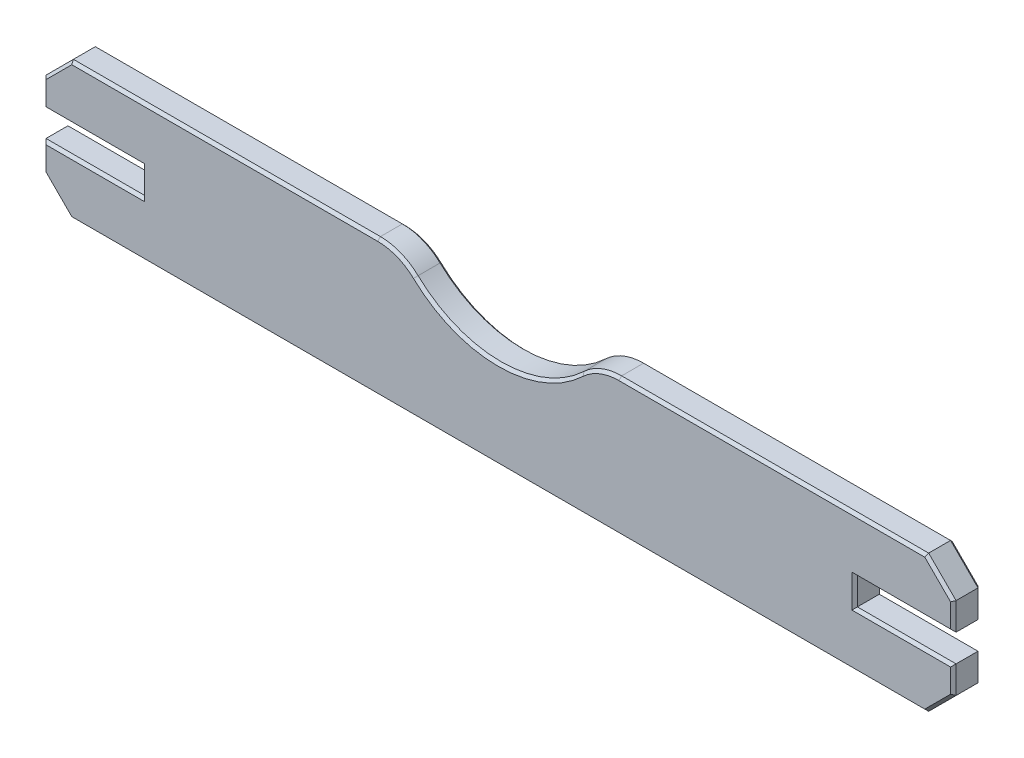
SolidWorks part; units mm, degrees
material "6061-T4 (SS)"
ref_plane "Front Plane" through (0, 0, 0) normal (0, 0, 1) x (1, 0, 0)
ref_plane "Top Plane" through (0, 0, 0) normal (0, 1, 0) x (1, 0, 0)
ref_plane "Right Plane" through (0, 0, 0) normal (1, 0, 0) x (0, 0, -1)
sketch "Sketch1" plane through (0, 0, 0) normal (0, 0, 1) x (1, 0, 0)
  line L0 (0, 46.3419) -> (0, 0) construction
  line L1 (0, 0) -> (-138.0781, 0) construction
  line L2 (-65, -2.5) -> (-65, 2.5)
  line L3 (-65, 2.5) -> (-83, 2.5)
  line L4 (-83, 2.5) -> (-83, 7.5)
  line L5 (-83, 7.5) -> (-78, 12.5)
  line L6 (-78, 12.5) -> (-22, 12.5)
  line L7 (-65, -2.5) -> (-83, -2.5)
  line L8 (-83, -2.5) -> (-83, -7.5)
  line L9 (-83, -7.5) -> (-78, -12.5)
  line L10 (-78, -12.5) -> (78, -12.5)
  line L11 (78, 12.5) -> (22, 12.5)
  line L12 (83, 7.5) -> (78, 12.5)
  line L13 (83, 2.5) -> (83, 7.5)
  line L14 (65, 2.5) -> (83, 2.5)
  line L15 (65, -2.5) -> (65, 2.5)
  line L16 (65, -2.5) -> (83, -2.5)
  line L17 (83, -2.5) -> (83, -7.5)
  line L18 (83, -7.5) -> (78, -12.5)
  arc A1 (-22, 12.5) -> (-15.125, 9.7618) centre (-22, 2.5) cw
  arc A2 (22, 12.5) -> (15.125, 9.7618) centre (22, 2.5) ccw
  arc A3 (-15.125, 9.7618) -> (15.125, 9.7618) centre (0, 25.7379) ccw
  point P15 (-65, 0)
  dimension "D1" = 22
  dimension "D2" = 10
  dimension "D3" = 56
  dimension "D4" = 2.5
  dimension "D5" = 12.5
  dimension "D6" = 130
  dimension "D7" = 18
  dimension "D8" = 5
  dimension "D9" = 5
extrude "Boss-Extrude1" add sketch "Sketch1" along normal blind 5
chamfer "Chamfer1" distance 0.5 angle 45 40 edges at (-18.2999, 11.7903, 0) (-50, 12.5, 0) (-80.5, 10, 0) (-83, 5, 0) (-74, 2.5, 0) (-65, 0, 0) (-74, -2.5, 0) (-83, -5, 0) (-80.5, -10, 0) (0, -12.5, 0) (80.5, -10, 0) (83, -5, 0) (74, -2.5, 0) (65, 0, 0) (74, 2.5, 0) (83, 5, 0) (80.5, 10, 0) (50, 12.5, 0) (18.2999, 11.7903, 0) (0, 3.7379, 0) (18.2999, 11.7903, 5) (50, 12.5, 5) (80.5, 10, 5) (83, 5, 5) (74, 2.5, 5) (65, 0, 5) (74, -2.5, 5) (83, -5, 5) (80.5, -10, 5) (0, -12.5, 5) (-80.5, -10, 5) (-83, -5, 5) (-74, -2.5, 5) (-65, 0, 5) (-74, 2.5, 5) (-83, 5, 5) (-80.5, 10, 5) (-50, 12.5, 5) (-18.2999, 11.7903, 5) (0, 3.7379, 5)
